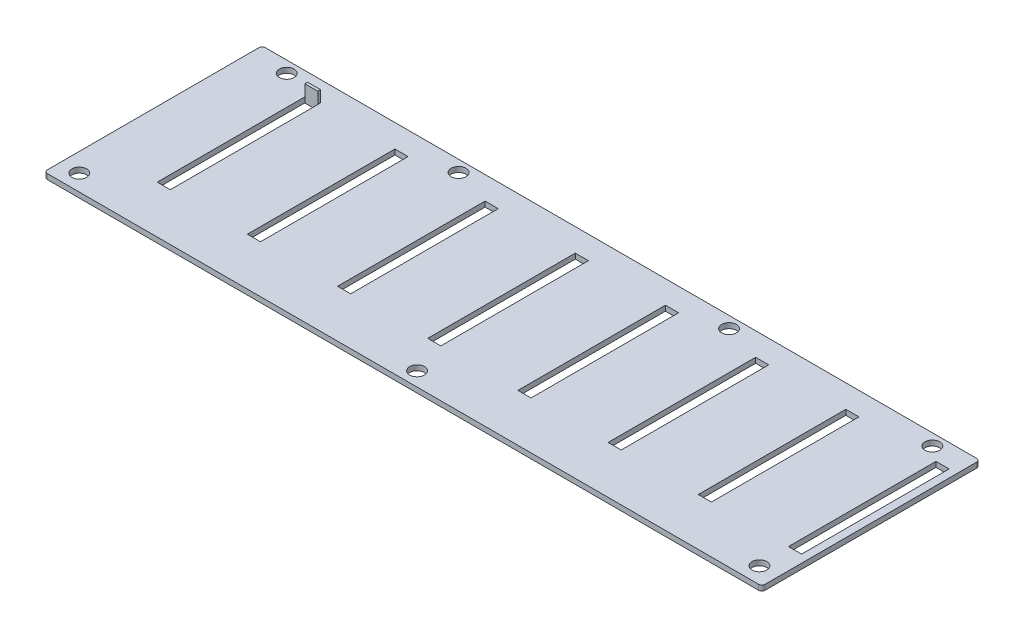
SolidWorks part; units mm, degrees
ref_plane "Front Plane" through (0, 0, 0) normal (0, 0, 1) x (1, 0, 0)
ref_plane "Top Plane" through (0, 0, 0) normal (0, 1, 0) x (1, 0, 0)
ref_plane "Right Plane" through (0, 0, 0) normal (1, 0, 0) x (0, 0, -1)
sketch "Sketch1" plane through (0, 0, 0) normal (0, 1, 0) x (1, 0, 0)
  line L0 (-343.6338, -10.1642) -> (262.3662, -10.1642) construction
  line L1 (0, 0) -> (218.9, 0)
  line L2 (0, 0) -> (0, 66.5)
  line L3 (0, 66.5) -> (218.9, 66.5)
  line L4 (218.9, 0) -> (218.9, 66.5)
  line L6 (20, 59.5) -> (24, 59.5)
  line L7 (20, 59.5) -> (20, 14.5)
  line L8 (20, 14.5) -> (24, 14.5)
  line L9 (24, 59.5) -> (24, 14.5)
  line L10 (47.5, 59.5) -> (51.5, 59.5)
  line L11 (47.5, 59.5) -> (47.5, 14.5)
  line L12 (47.5, 14.5) -> (51.5, 14.5)
  line L13 (51.5, 59.5) -> (51.5, 14.5)
  line L14 (75, 59.5) -> (79, 59.5)
  line L15 (75, 59.5) -> (75, 14.5)
  line L16 (75, 14.5) -> (79, 14.5)
  line L17 (79, 59.5) -> (79, 14.5)
  line L18 (102.5, 59.5) -> (106.5, 59.5)
  line L19 (102.5, 59.5) -> (102.5, 14.5)
  line L20 (102.5, 14.5) -> (106.5, 14.5)
  line L21 (106.5, 59.5) -> (106.5, 14.5)
  line L22 (130, 59.5) -> (134, 59.5)
  line L23 (130, 59.5) -> (130, 14.5)
  line L24 (130, 14.5) -> (134, 14.5)
  line L25 (134, 59.5) -> (134, 14.5)
  line L26 (157.5, 59.5) -> (161.5, 59.5)
  line L27 (157.5, 59.5) -> (157.5, 14.5)
  line L28 (157.5, 14.5) -> (161.5, 14.5)
  line L29 (161.5, 59.5) -> (161.5, 14.5)
  line L30 (185, 59.5) -> (189, 59.5)
  line L31 (185, 59.5) -> (185, 14.5)
  line L32 (185, 14.5) -> (189, 14.5)
  line L33 (189, 59.5) -> (189, 14.5)
  line L34 (212.5, 59.5) -> (216.5, 59.5)
  line L35 (212.5, 59.5) -> (212.5, 14.5)
  line L36 (212.5, 14.5) -> (216.5, 14.5)
  line L37 (216.5, 59.5) -> (216.5, 14.5)
  circle A0 centre (11, 63) radius 2.25
  circle A1 centre (63.4, 63) radius 2.25
  circle A2 centre (145.9, 63) radius 2.25
  circle A3 centre (207.9, 63) radius 2.25
  circle A4 centre (5.75, 5) radius 2.25
  circle A5 centre (109.45, 4.3) radius 2.25
  circle A6 centre (213.15, 5) radius 2.25
  dimension "D3" = 3.5
  dimension "D5" = 3.5
  dimension "D7" = 3.5
  dimension "D9" = 3.5
  dimension "D11" = 5
  dimension "D13" = 4.3
  dimension "D15" = 5
  dimension "D1" = 218.9
  dimension "D2" = 66.5
  dimension "D4" = 11
  dimension "D6" = 52.4
  dimension "D8" = 82.5
  dimension "D10" = 62
  dimension "D12" = 5.75
  dimension "D14" = 103.7
  dimension "D16" = 103.7
  dimension "D17" = 4
  dimension "D18" = 45
  dimension "D19" = 20
  dimension "D20" = 7
  dimension "D21" = 27.5
  dimension "D22" = 4
  dimension "D23" = 45
  dimension "D24" = 7
  dimension "D25" = 4
  dimension "D26" = 45
  dimension "D27" = 7
  dimension "D28" = 27.5
  dimension "D29" = 27.5
  dimension "D30" = 4
  dimension "D31" = 45
  dimension "D32" = 7
  dimension "D33" = 27.5
  dimension "D34" = 45
  dimension "D35" = 4
  dimension "D36" = 7
  dimension "D37" = 27.5
  dimension "D38" = 4
  dimension "D39" = 45
  dimension "D40" = 7
  dimension "D41" = 27.5
  dimension "D42" = 4
  dimension "D43" = 45
  dimension "D44" = 7
  dimension "D45" = 45
  dimension "D46" = 7
  dimension "D47" = 27.5
  dimension "D48" = 4
extrude "Boss-Extrude1" add sketch "Sketch1" along normal blind 1.6
fillet "Fillet1" radius 1 4 edges at (218.9, 0.8, -66.5) (218.9, 0.8, 0) (0, 0.8, 0) (0, 0.8, -66.5)
ref_plane "Plane1" through (20, 1.6, -14.5) normal (0, 0, 1) x (1, 0, 0)
sketch "Sketch3" plane through (0, 0, 0) normal (0, 1, 0) x (1, 0, 0)
  line L1 (20, 59.5) -> (24, 59.5)
  line L2 (20, 59.5) -> (20, 60.3316)
  line L3 (20, 60.3316) -> (24, 60.3316)
  line L4 (24, 59.5) -> (24, 60.3316)
  dimension "D1" = 4
extrude "Boss-Extrude2" add sketch "Sketch3" along normal blind 5.1
